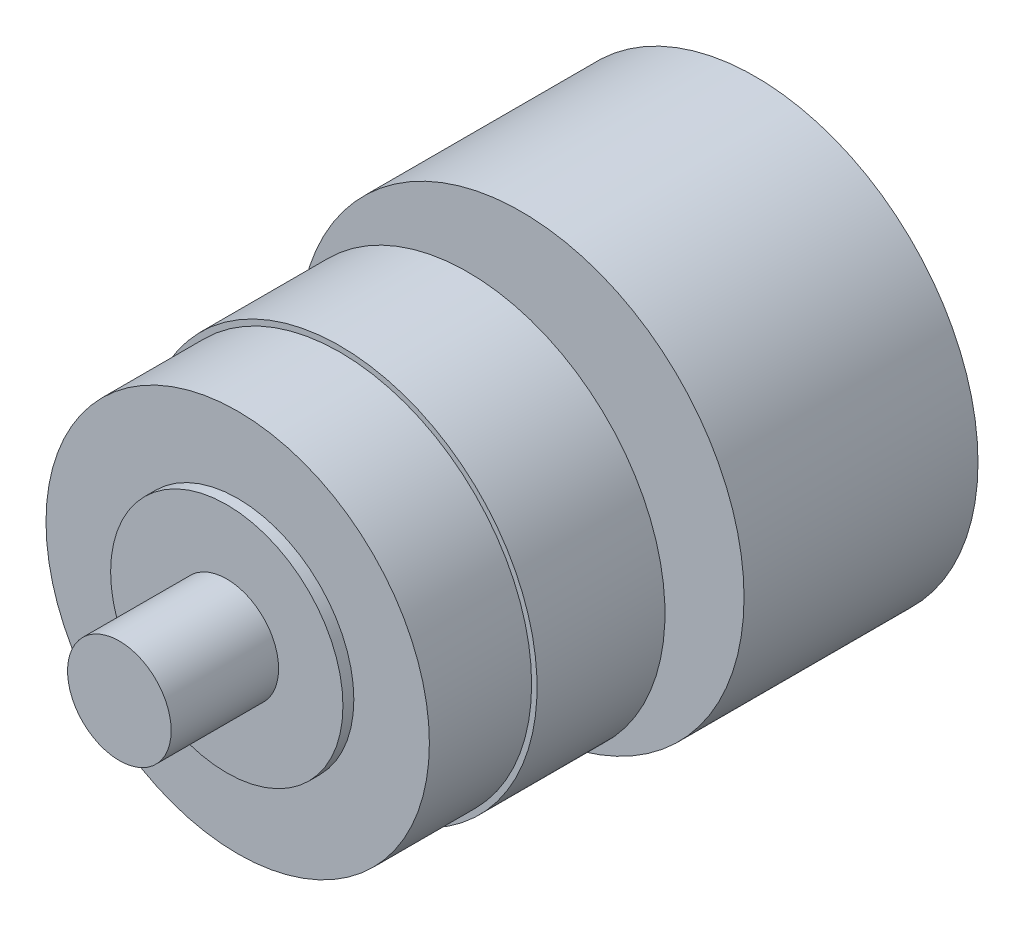
SolidWorks part; units mm, degrees
material "Nylon 6/10"
ref_plane "Front" through (0, 0, 0) normal (0, 0, 1) x (1, 0, 0)
ref_plane "Top" through (0, 0, 0) normal (0, 1, 0) x (1, 0, 0)
ref_plane "Right" through (0, 0, 0) normal (1, 0, 0) x (0, 0, -1)
sketch "Sketch1" plane through (0, 0, 0) normal (0, 0, 1) x (1, 0, 0)
  circle A0 centre (0, 0) radius 2.413
  dimension "D1" = 4.826
extrude "Extrude1" add sketch "Sketch1" against normal blind 5.0038
sketch "Sketch2" plane through (0, 0, -5.0038) normal (0, 0, -1) x (-1, 0, 0)
  circle A0 centre (0, 0) radius 5.4102
  dimension "D1" = 10.8204
extrude "Extrude2" add sketch "Sketch2" along normal blind 0.508
sketch "Sketch3" plane through (0, 0, -5.5118) normal (0, 0, -1) x (-1, 0, 0)
  circle A0 centre (0, 0) radius 8.9281
extrude "Extrude3" add sketch "Sketch3" along normal blind 4.7625
sketch "Sketch4" plane through (0, 0, -10.2743) normal (0, 0, -1) x (-1, 0, 0)
  circle A0 centre (0, 0) radius 9.1821
extrude "Extrude4" add sketch "Sketch4" along normal blind 5.9563
sketch "Sketch6" plane through (0, 0, -16.2306) normal (0, 0, -1) x (-1, 0, 0)
  circle A0 centre (0, 0) radius 6.35
  dimension "D1" = 12.7
extrude "Extrude5" add sketch "Sketch6" along normal blind 2.2352 draft 45
sketch "Sketch7" plane through (0, 0, -18.4658) normal (0, 0, -1) x (-1, 0, 0)
  circle A0 centre (0, 0) radius 4.1148
  circle A2 centre (0, 0) radius 4.1148 construction
extrude "Extrude6" add sketch "Sketch7" along normal blind 0.254
sketch "Sketch8" plane through (0, 0, -18.7198) normal (0, 0, -1) x (-1, 0, 0)
  circle A0 centre (0, 0) radius 10.3759
  dimension "D1" = 20.7518
extrude "Extrude7" add sketch "Sketch8" along normal blind 10.8966
sketch "Sketch9" plane through (0, 0, -29.6164) normal (0, 0, -1) x (-1, 0, 0)
  circle A0 centre (0, 0) radius 5.08
  dimension "D1" = 10.16
extrude "Extrude8" add sketch "Sketch9" along normal blind 0.127
sketch "Sketch10" plane through (0, 0, -29.7434) normal (0, 0, -1) x (-1, 0, 0)
  line L1 (7.3323, 0) -> (3.6662, 6.35)
  line L2 (3.6662, 6.35) -> (-3.6662, 6.35)
  line L3 (-3.6662, 6.35) -> (-7.3323, 0)
  line L4 (-7.3323, 0) -> (-3.6662, -6.35)
  line L5 (-3.6662, -6.35) -> (3.6662, -6.35)
  line L6 (3.6662, -6.35) -> (7.3323, 0)
  circle A0 centre (0, 0) radius 6.35 construction
  dimension "D1" = 12.7
extrude "Extrude9" add sketch "Sketch10" along normal blind 1.524
sketch "Sketch11" plane through (0, 0, -31.2674) normal (0, 0, -1) x (-1, 0, 0)
  circle A0 centre (0, 0) radius 6.3373
  dimension "D1" = 12.6746
extrude "Cut-Extrude1" cut sketch "Sketch11" against normal blind 1.524 draft 45 flip side to cut
ref_plane "giude face" through (0, 0, -17.7292) normal (0, 0, -1) x (-1, 0, 0)
